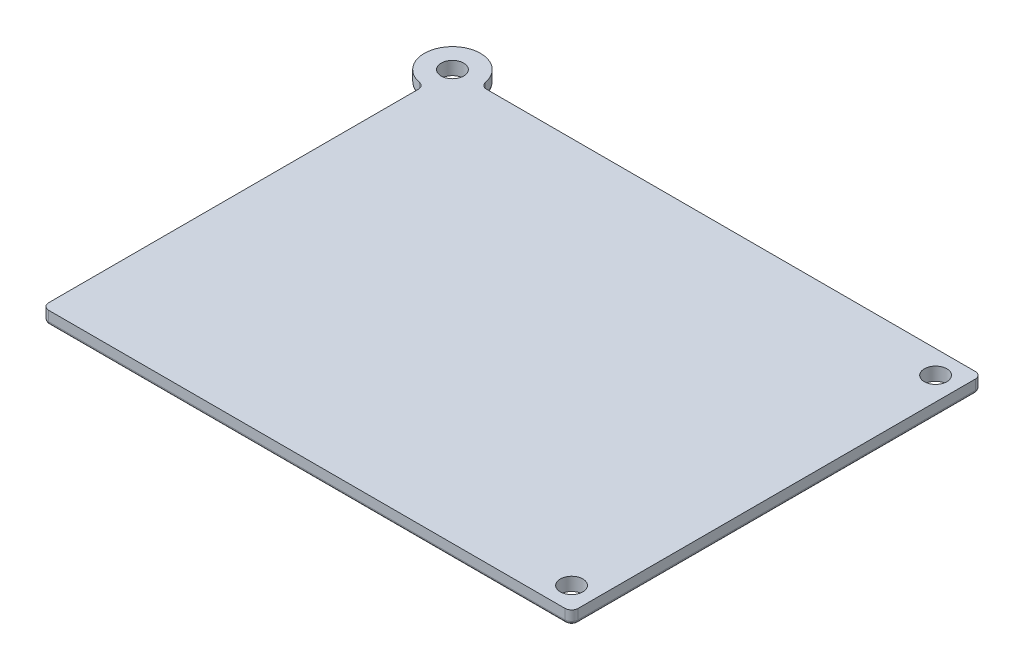
SolidWorks part; units mm, degrees
material "PVC Rigid"
ref_plane "Front Plane" through (0, 0, 0) normal (0, 0, 1) x (1, 0, 0)
ref_plane "Top Plane" through (0, 0, 0) normal (0, 1, 0) x (1, 0, 0)
ref_plane "Right Plane" through (0, 0, 0) normal (1, 0, 0) x (0, 0, -1)
sketch "Sketch1" plane through (0, 0, 0) normal (0, 1, 0) x (1, 0, 0)
  line L1 (-40, -31) -> (40, -31)
  line L2 (-40, -31) -> (-40, 25.8461)
  line L3 (-34.8461, 31) -> (40, 31)
  line L4 (40, -31) -> (40, 31)
  line L5 (-40, -31) -> (40, 31) construction
  line L6 (0, 0) -> (40, -31) construction
  arc A0 (-40, 25.8461) -> (-40.8095, 26.8278) centre (-41, 25.8461) ccw construction
  arc A1 (-35.8278, 31.8095) -> (-34.8461, 31) centre (-34.8461, 32) ccw construction
  arc A2 (-35.8278, 31.8095) -> (-40.8095, 26.8278) centre (-40, 31) ccw construction
  arc A3 (-40, 25.8461) -> (-40.8095, 26.8278) centre (-41, 25.8461) ccw
  arc A4 (-35.8278, 31.8095) -> (-34.8461, 31) centre (-34.8461, 32) ccw
  arc A5 (-35.8278, 31.8095) -> (-40.8095, 26.8278) centre (-40, 31) ccw
  point P0 (0, 0)
  dimension "D1" = 80
  dimension "D2" = 62
extrude "Main Body" add sketch "Sketch1" along normal blind 2
fillet "Corners" radius 1 3 edges at (-40, 1, 31) (40, 1, -31) (40, 1, 31)
fillet "Edge" radius 0.5 10 edges at (-39.7071, 0, 30.7071) (39.7071, 0, -30.7071) (39.7071, 0, 30.7071) (-40, 0, 2.0769) (2.0769, 0, -31) (40, 0, 0) (0, 0, 31) (-40.2285, 0, -26.4823) (-43.0052, 0, -34.0052) (-35.4823, 0, -31.2285)
sketch "Sketch7" plane through (0, 0, 0) normal (0, -1, 0) x (-1, 0, 0)
  line L0 (-39, 31) -> (34.8461, 31) construction
  line L1 (-40, -30) -> (-40, 30) construction
  line L2 (39, -31) -> (-39, -31) construction
  circle A0 centre (-36.5, 27.5) radius 1.7
  circle A1 centre (-36.5, -27.5) radius 1.7
  arc A2 (40.7143, 27.3187) -> (36.3187, 31.7143) centre (40, 31) ccw construction
  circle A4 centre (40, 31) radius 1.7
  dimension "D3" = 3.4
  dimension "D4" = 3.4
  dimension "D6" = 3.4
  dimension "D1" = 3.5
  dimension "D2" = 3.5
  dimension "D5" = 3.5
extrude "Lid Holes" cut sketch "Sketch7" against normal through all both and the other way through all
sketch "CHANGE ME TO ALTER PEG ANGLE" plane through (0, 0, 0) normal (0, -1, 0) x (-1, 0, 0)
  line L0 (39.5, -30) -> (25.9753, -15.2663) construction
  line L1 (-39.3536, -30.3536) -> (-25.6372, -15.7981) construction
  line L2 (-39.5, 30) -> (-39.5, -30) construction
  line L3 (40, 25.8461) -> (40, -30) construction
  arc A0 (-39.5, -30) -> (-39, -30.5) centre (-39, -30) ccw construction
  dimension "D1" = 43.3
  dimension "D2" = 20
  dimension "D3" = 20
  dimension "D4" = 42.55
sketch "Sketch4" plane through (0, 0, 0) normal (0, -1, 0) x (-1, 0, 0)
  line L0 (-39.3536, -30.3536) -> (-25.6372, -15.7981) construction
  line L3 (-34.7206, -19.6048) -> (-28.8985, -25.0913) construction
  circle A0 centre (-34.7206, -19.6048) radius 2.325
  circle A1 centre (-28.8985, -25.0913) radius 2.325
  point P8 (-31.8096, -22.3481)
  dimension "D1" = 4.65
  dimension "D3" = 4.65
  dimension "D2" = 4
  dimension "D4" = 8
  dimension "D5" = 11
extrude "Boss-Extrude3" add sketch "Sketch4" along normal blind 1.6
fillet "Fillet3" radius 0.05 2 edges at (34.7206, -1.6, 17.2798) (28.8985, -1.6, 22.7663)
pattern_linear "LPattern5" count 4 spacing 8 along (-0.6858, 0, -0.7278) of "Boss-Extrude3", "Fillet3"
sketch "Sketch9" plane through (0, 0, 0) normal (0, -1, 0) x (-1, 0, 0)
  line L0 (39.5, -30) -> (25.9753, -15.2663) construction
  line L2 (28.2092, -23.6149) -> (34.1027, -18.2051) construction
  circle A0 centre (28.2092, -23.6149) radius 2.325
  circle A1 centre (34.1027, -18.2051) radius 2.325
  arc A2 (39, -31) -> (40, -30) centre (39, -30) ccw construction
  point P8 (31.1559, -20.91)
  point P11 (39.7071, -30.7071)
  dimension "D1" = 4.65
  dimension "D2" = 4.65
  dimension "D3" = 8
  dimension "D4" = 13
extrude "Pegs (Diagonal)" add sketch "Sketch9" along normal blind 1.6
fillet "Fillet6" radius 0.05 2 edges at (-28.2092, -1.6, 21.2899) (-34.1027, -1.6, 15.8801)
pattern_linear "LPattern6" count 4 spacing 8 along (0.6762, 0, -0.7367) of "Pegs (Diagonal)"
sketch "Alignment points" plane through (0, 0, 0) normal (0, -1, 0) x (-1, 0, 0)
  line L0 (-23.7475, -7.9604) -> (-17.9254, -13.447) construction
  line L1 (-29.2341, -13.7826) -> (-23.4119, -19.2691) construction
  line L2 (-26.323, -16.5259) -> (-20.8365, -10.7037) construction
  line L3 (23.283, -6.4181) -> (17.3895, -11.8279) construction
  line L4 (28.6928, -12.3116) -> (22.7993, -17.7214) construction
  line L5 (20.3362, -9.123) -> (25.7461, -15.0165) construction
  point P0 (-23.5797, -13.6148)
  point P1 (23.0411, -12.0697)
  point P12 (-23.5797, -13.6148)
  point P23 (23.0411, -12.0697)
sketch "Alignment points streamlined" plane through (0, 0, 0) normal (0, -1, 0) x (-1, 0, 0)
  point P0 (-23.5797, -13.6148)
  point P1 (23.0411, -12.0697)
ref_axis "Alignment Axes 1" through (23.5797, 0, 13.6148) along (0, -1, 0)
ref_axis "Alignment Axes 2 Electric Boogaloo" through (-23.0411, 0, 12.0697) along (0, -1, 0)
equation "\"D2@Sketch9\"=\"D1@Sketch9\""
equation "\"D3@Sketch4\"=\"D1@Sketch4\""
equation "\"D4@Sketch4\"=\"D2@Sketch4\"*2"
equation "\"D4@Sketch7\"=\"D3@Sketch7\""
equation "\"D5@Sketch7\"=\"D1@Sketch7\""
equation "\"D6@Sketch7\"=\"D3@Sketch7\""
